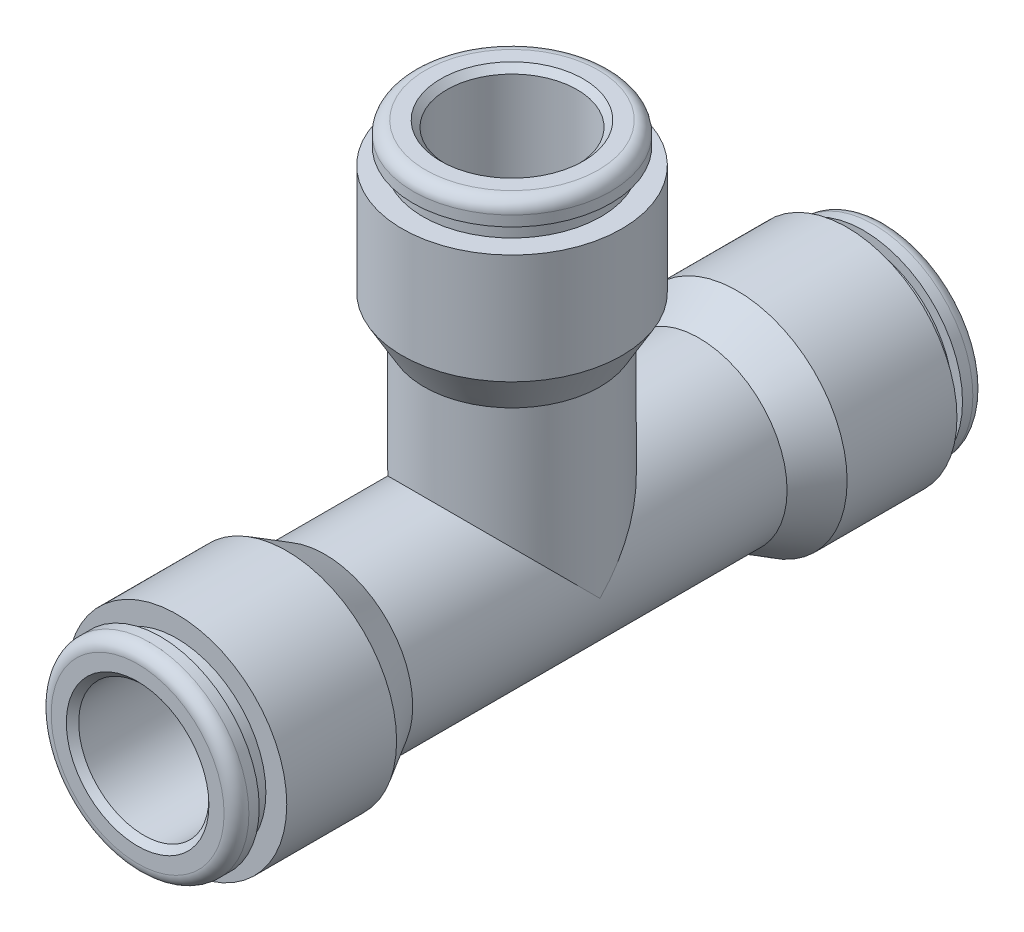
SolidWorks part; units mm, degrees
ref_plane "Front Plane" through (0, 0, 0) normal (0, 0, 1) x (1, 0, 0)
ref_plane "Top Plane" through (0, 0, 0) normal (0, 1, 0) x (1, 0, 0)
ref_plane "Right Plane" through (0, 0, 0) normal (1, 0, 0) x (0, 0, -1)
sketch "Sketch1" plane through (0, 0, 0) normal (1, 0, 0) x (0, 0, -1)
  line L0 (21.603, 6.075) -> (22.238, 6.075)
  line L1 (13.8383, 6.75) -> (20.587, 6.75)
  line L2 (0, 5.4) -> (0, 3.238)
  line L3 (6.9, 4) -> (22.619, 4)
  line L4 (23, 5.313) -> (23, 4.381)
  line L5 (0, 0) -> (0, 22.75) construction
  line L6 (20.587, 6.75) -> (20.587, 5.4675)
  line L7 (20.587, 5.4675) -> (21.603, 5.4675)
  line L8 (21.603, 6.075) -> (21.603, 5.4675)
  line L9 (-6.75, 22.75) -> (6.75, 22.75) construction
  line L10 (0, 0) -> (23, 0) construction
  line L11 (6.9, 4) -> (6.9, 3.238)
  line L12 (22.619, 4) -> (23, 4.381)
  line L13 (0, 0) -> (0, 3.238) construction
  line L14 (0, 5.4) -> (11.5, 5.4)
  line L15 (11.5, 5.4) -> (13.8383, 6.75)
  line L16 (6.9, 3.238) -> (0, 3.238)
  line L17 (0, 23) -> (0, 0) construction
  line L22 (0, 0) -> (-23, 0) construction
  arc A0 (22.238, 6.075) -> (23, 5.313) centre (22.238, 5.313) cw
  point P1 (23, 4)
  point P2 (23, 6.75)
  point P17 (23, -6.75)
  point P20 (23, 6.075)
  point P26 (-23, -6.75)
  dimension "D4" = 0.762
  dimension "tube od" = 8
  dimension "D1" = 1.397
  dimension "D2" = 1.016
  dimension "D3" = 10.935
  dimension "D6" = 12.15
  dimension "D9" = 30
  dimension "D10" = 10.8
  dimension "D5" = 11.5
  dimension "D8" = 13.5
  dimension "D11" = 0.762
revolve "Revolve1" add sketch "Sketch1" angle 360 about L10
ref_axis "Axis1" through (-6.05, 0, 0) along (1, 0, 0)
pattern_circular "CirPattern1" count 3 over 180 about axis through (-6.05, 0, 0) along (1, 0, 0) of bodies 118 123
move or copy body "Body-Move/Copy1" bodies to move or copy 124 copy no translate (0, -0.25, 0)
sketch "Sketch3" plane through (0, 0, 0) normal (0, 1, 0) x (1, 0, 0)
  circle A0 centre (0, 0) radius 5.4 construction
  circle A1 centre (0, 0) radius 5.4
extrude "Cut-Extrude2" cut sketch "Sketch3" against normal through all and the other way blind 0.1 draft 45
sketch "Sketch4" plane through (0, 0, 0) normal (1, 0, 0) x (0, 0, -1)
  line L0 (4, 22.369) -> (4.381, 22.75)
  line L1 (4.381, 22.75) -> (0, 22.75)
  line L2 (0, 22.75) -> (0, 0)
  line L4 (3.238, 0) -> (3.238, 6.65)
  line L5 (3.238, 6.65) -> (4, 6.65)
  line L6 (4, 6.65) -> (4, 22.369)
  line L7 (3.238, 0) -> (0, 0)
  line L9 (3.238, 6.65) -> (-3.238, 6.65) construction
  line L10 (4, 6.65) -> (-4, 6.65) construction
revolve "Cut-Revolve2" cut sketch "Sketch4" angle 360 about L5
combine bodies "Combine1" operation type add bodies to combine 145 144 146
sketch "Sketch5" plane through (0, 0, 0) normal (1, 0, 0) x (0, 0, -1)
  line L0 (23, 4.381) -> (22.619, 4)
  line L1 (22.619, 4) -> (6.9, 4)
  line L2 (6.9, 4) -> (6.9, 3.238)
  line L3 (6.9, 3.238) -> (0, 3.238)
  line L4 (0, 3.238) -> (0, 0)
  line L5 (0, 0) -> (23, 0)
  line L6 (23, 0) -> (23, 4.381)
revolve "Cut-Revolve1" cut sketch "Sketch5" angle 360 about L5
pattern_circular "CirPattern2" count 2 over 180 about axis through (-6.05, 0, 0) along (1, 0, 0) of "Cut-Revolve1"
equation "\"D6@Sketch1\" = \"G@Sketch1\"*.9"
equation "\"D3@Sketch1\" = \"D6@Sketch1\"*.9"
equation "\"D10@Sketch1\" = \"G@Sketch1\"*.8"
equation "\"D5@Sketch1\" = \"L/2@Sketch1\"*.5"
equation "\"D8@Sketch1\" = \"G@Sketch1\""
